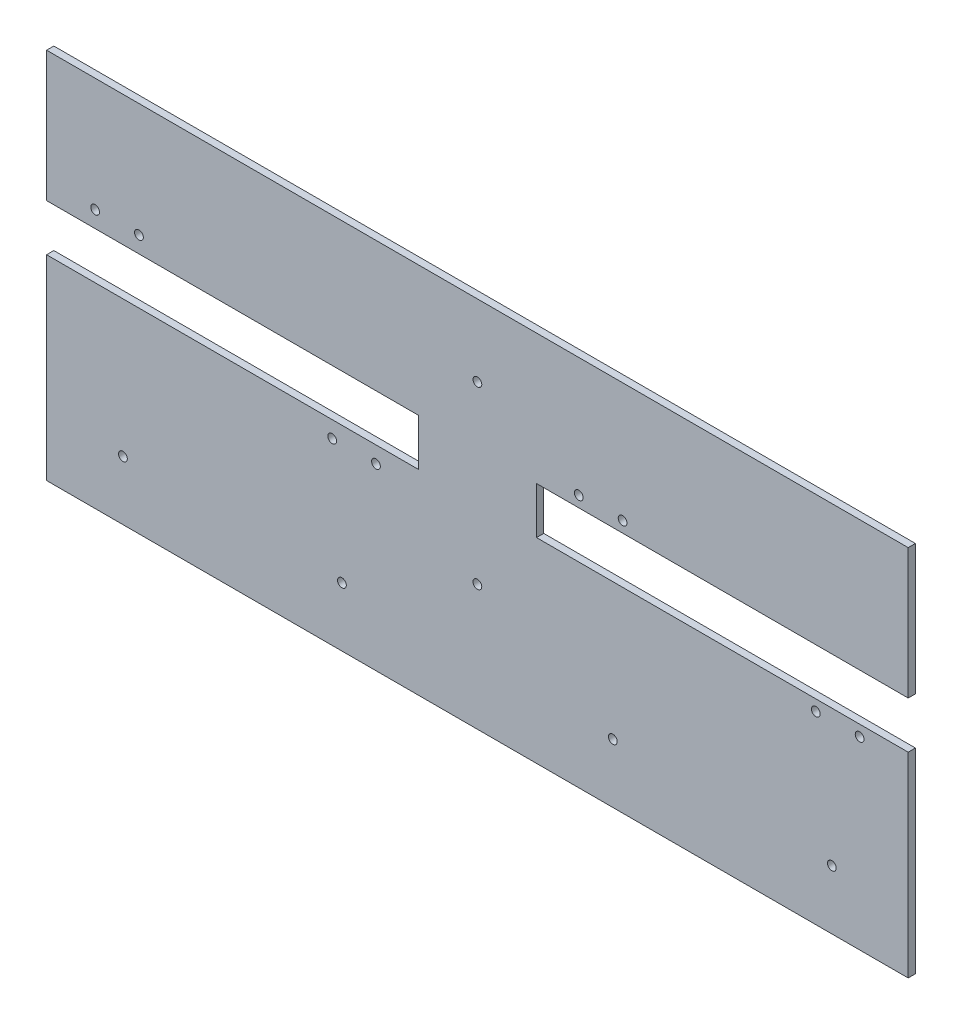
SolidWorks part; units mm, degrees
material "Balsa"
ref_plane "Front Plane" through (0, 0, 0) normal (0, 0, 1) x (1, 0, 0)
ref_plane "Top Plane" through (0, 0, 0) normal (0, 1, 0) x (1, 0, 0)
ref_plane "Right Plane" through (0, 0, 0) normal (1, 0, 0) x (0, 0, -1)
sketch "Sketch1" plane through (0, 0, 0) normal (0, 0, 1) x (1, 0, 0)
  line L1 (223.7, -24.5) -> (-169.7, -24.5)
  line L2 (223.7, -24.5) -> (223.7, 145.6824)
  line L3 (223.7, 145.6824) -> (-169.7, 145.6824)
  line L4 (-169.7, -24.5) -> (-169.7, 145.6824)
  line L5 (223.7, -24.5) -> (-169.7, 145.6824) construction
  line L6 (223.7, 145.6824) -> (-169.7, -24.5) construction
  line L7 (227, -24.5) -> (223.7, -24.5) construction
  line L9 (223.7, 145.6824) -> (54, 145.6824) construction
  line L10 (223.7, 144.1231) -> (223.7, -24.5) construction
  line L11 (-169.7, -24.5) -> (-169.7, 144.1269) construction
  point P4 (27, 60.5912)
extrude "Boss-Extrude1" add sketch "Sketch1" along normal up to surface (3.3 mm away)
sketch "Sketch2" plane through (0, 0, 0) normal (0, 0, -1) x (-1, 0, 0)
  line L0 (-223.7, 145.6824) -> (169.7, 145.6824) construction
  line L1 (0, 0) -> (-54, 0)
  line L2 (0, 0) -> (0, 145.6824)
  line L3 (0, 145.6824) -> (-54, 145.6824)
  line L4 (-54, 0) -> (-54, 145.6824)
  line L5 (0, 0) -> (-54, 145.6824) construction
  line L6 (0, 145.6824) -> (-54, 0) construction
  line L7 (-54, 262.7) -> (-54, 0) construction
  line L8 (-27, 0) -> (-27, 145.6824) construction
  line L9 (169.7, 145.6824) -> (169.7, -24.5) construction
  line L10 (-223.7, 29.5) -> (-54, 29.5)
  line L11 (-223.7, 29.5) -> (-223.7, -24.5)
  line L12 (-223.7, -24.5) -> (-54, -24.5)
  line L13 (-54, 29.5) -> (-54, -24.5)
  line L14 (-223.7, 29.5) -> (-54, -24.5) construction
  line L15 (-223.7, -24.5) -> (-54, 29.5) construction
  line L16 (169.7, 29.5) -> (0, 29.5)
  line L17 (169.7, 29.5) -> (169.7, -24.5)
  line L18 (169.7, -24.5) -> (0, -24.5)
  line L19 (0, 29.5) -> (0, -24.5)
  line L20 (169.7, 29.5) -> (0, -24.5) construction
  line L21 (169.7, -24.5) -> (0, 29.5) construction
  line L22 (-223.7, 2.5) -> (169.7, 2.5) construction
  line L23 (-138.85, -24.5) -> (-138.85, 29.5) construction
  circle A0 centre (-27, 32.8412) radius 2
  circle A1 centre (-27, 112.8412) radius 2
  circle A2 centre (-188.85, 2.5) radius 2
  circle A3 centre (-88.85, 2.5) radius 2
  circle A4 centre (34.85, 2.5) radius 2
  circle A5 centre (134.85, 2.5) radius 2
  point P4 (-27, 72.8412)
  point P20 (-138.85, 2.5)
  point P27 (84.85, 2.5)
  dimension "D1" = 4
  dimension "D2" = 4
  dimension "D3" = 40
  dimension "D4" = 40
  dimension "D5" = 4
  dimension "D6" = 50
extrude "Cut-Extrude1" cut sketch "Sketch2" against normal blind 4 contours A1 | A0 | A2 | A3 | A5 | A4
sketch "Sketch3" plane through (0, 0, 0) normal (0, 0, -1) x (-1, 0, 0)
  line L0 (169.7, 145.6824) -> (169.7, -24.5) construction
  line L1 (169.7, 64.8) -> (-223.7, 64.8)
  line L2 (169.7, 64.8) -> (169.7, 86.2)
  line L3 (169.7, 86.2) -> (-223.7, 86.2)
  line L4 (-223.7, 64.8) -> (-223.7, 86.2)
  line L5 (169.7, 64.8) -> (-223.7, 86.2) construction
  line L6 (169.7, 86.2) -> (-223.7, 64.8) construction
  line L7 (-223.7, -24.5) -> (-223.7, 145.6824) construction
  line L8 (35.8344, 64.8) -> (9.0983, 64.8) construction
  line L9 (142.922, 86.2) -> (163.7817, 86.2) construction
  line L10 (0, 64.8) -> (0, 86.2)
  line L11 (-54, 64.8) -> (-54, 86.2)
  line L12 (-54, 262.7) -> (-54, 0) construction
  line L13 (0, 262.7) -> (0, 0) construction
  line L14 (0, 262.7) -> (0, 0) construction
  point P4 (-27, 75.5)
  line M7 (-223.7, 145.6824) -> (-223.7, -24.5)
  line M9 (169.7, -24.5) -> (169.7, 145.6824)
extrude "Cut-Extrude2" cut sketch "Sketch3" against normal blind 6 contours L10 L1 L3 M9 | L1 L11 L3 M7 region at (-84.85, 75.5, 0) region at (138.85, 75.5, 0)
sketch "Sketch4" plane through (0, 0, 3.3) normal (0, 0, 1) x (1, 0, 0)
  circle A0 centre (93.3034, 91.2) radius 2
  circle A1 centre (73.3034, 91.2) radius 2
  circle A2 centre (181.5258, 59.8) radius 2
  circle A3 centre (201.5258, 59.8) radius 2
  circle A4 centre (-127.5258, 93.7) radius 2
  circle A5 centre (-147.5258, 93.7) radius 2
  circle A6 centre (-19.3034, 57.3) radius 2
  circle A7 centre (-39.3034, 57.3) radius 2
  circle A8 centre (-39.3034, 57.3) radius 2 construction
  circle A9 centre (-19.3034, 57.3) radius 2 construction
  circle A10 centre (-127.5258, 93.7) radius 2 construction
  circle A11 centre (-147.5258, 93.7) radius 2 construction
  circle A12 centre (181.5258, 59.8) radius 2 construction
  circle A13 centre (93.3034, 91.2) radius 2 construction
  circle A14 centre (73.3034, 91.2) radius 2 construction
  circle A15 centre (201.5258, 59.8) radius 2 construction
extrude "Cut-Extrude3" cut sketch "Sketch4" against normal through all
